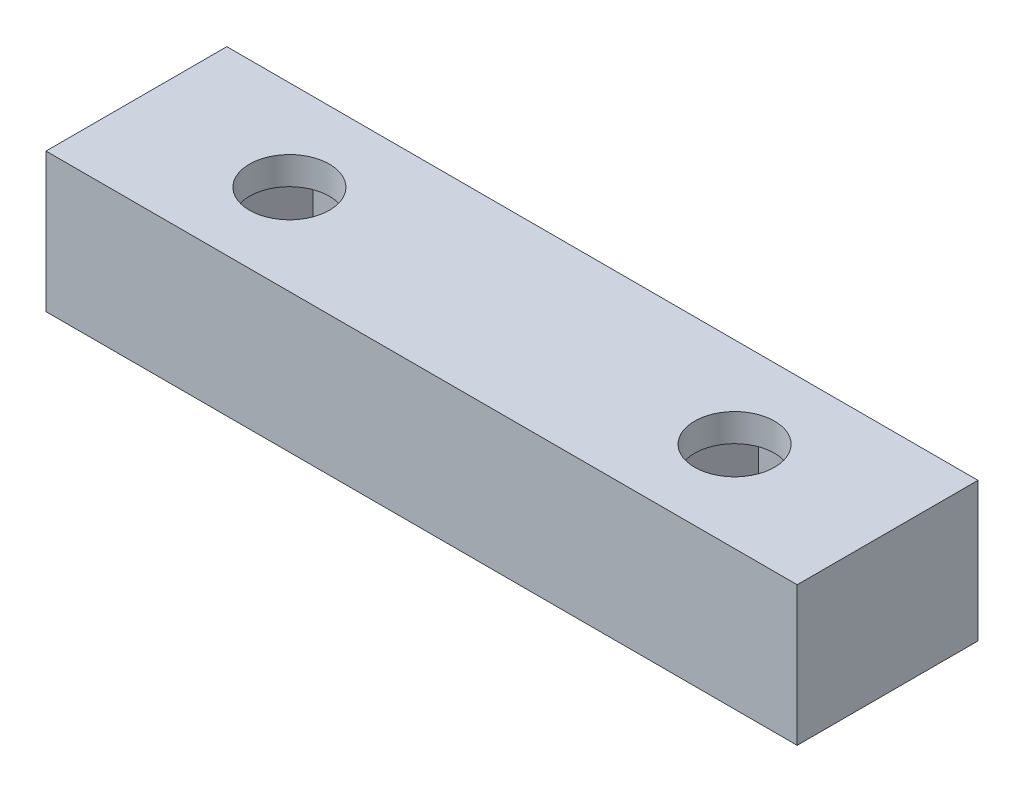
SolidWorks part; units mm, degrees
ref_plane "Front" through (0, 0, 0) normal (0, 0, 1) x (1, 0, 0)
ref_plane "Top" through (0, 0, 0) normal (0, 1, 0) x (1, 0, 0)
ref_plane "Right" through (0, 0, 0) normal (1, 0, 0) x (0, 0, -1)
sketch "Croquis1" plane through (0, 0, 0) normal (0, 1, 0) x (1, 0, 0)
  line L0 (-16, 0) -> (16, 0)
  line L1 (-27, 6.5) -> (27, 6.5)
  line L2 (-27, 6.5) -> (-27, -6.5)
  line L3 (-27, -6.5) -> (27, -6.5)
  line L4 (27, 6.5) -> (27, -6.5)
  line L5 (-27, 6.5) -> (27, -6.5) construction
  line L6 (-27, -6.5) -> (27, 6.5) construction
  line L8 (-18.3383, -4.05) -> (-13.6617, -4.05)
  line L9 (-13.6617, -4.05) -> (-11.3235, 0)
  line L10 (-11.3235, 0) -> (-13.6617, 4.05)
  line L11 (-13.6617, 4.05) -> (-18.3383, 4.05)
  line L12 (-18.3383, 4.05) -> (-20.6765, 0)
  line L13 (-20.6765, 0) -> (-18.3383, -4.05)
  line L14 (20.6765, 0) -> (18.3383, 4.05)
  line L15 (18.3383, 4.05) -> (13.6617, 4.05)
  line L16 (13.6617, 4.05) -> (11.3235, 0)
  line L17 (11.3235, 0) -> (13.6617, -4.05)
  line L18 (13.6617, -4.05) -> (18.3383, -4.05)
  line L19 (18.3383, -4.05) -> (20.6765, 0)
  circle A0 centre (-16, 0) radius 4.05 construction
  circle A1 centre (16, 0) radius 4.05 construction
  circle A2 centre (-16, 0) radius 2.875
  circle A3 centre (16, 0) radius 2.875
  point P0 (0, 0)
  point P9 (0, 0)
  dimension "D5" = 5.75
  dimension "D6" = 5.75
  dimension "D1" = 13
  dimension "D2" = 32
  dimension "D3" = 54
  dimension "D4" = 8.1
extrude "Saliente-Extruir1" add sketch "Croquis1" along normal blind 10 contours L3 L4 L1 L2
extrude "Cortar-Extruir1" cut sketch "Croquis1<3>" along normal blind 8 contours L8 L9 L10 L11 L12 L13 | L14 L15 L16 L17 L18 L19
sketch "Croquis1<3>" plane through (0, 0, 0) normal (0, 1, 0) x (1, 0, 0) same geometry as "Croquis1"
extrude "Cortar-Extruir2" cut sketch "Croquis1<4>" along normal through all contours A2 | A3
sketch "Croquis1<4>" plane through (0, 0, 0) normal (0, 1, 0) x (1, 0, 0) same geometry as "Croquis1"
